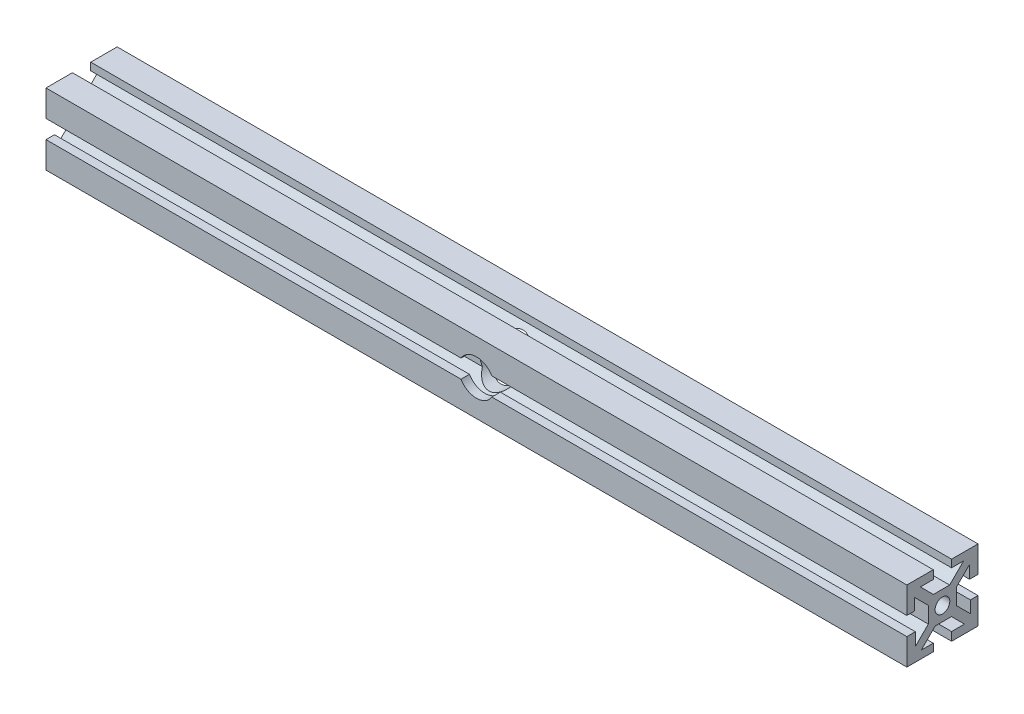
SolidWorks part; units mm, degrees
material "6061 Alloy"
ref_plane "Front Plane" through (0, 0, 0) normal (0, 0, 1) x (1, 0, 0)
ref_plane "Top Plane" through (0, 0, 0) normal (0, 1, 0) x (1, 0, 0)
ref_plane "Right Plane" through (0, 0, 0) normal (1, 0, 0) x (0, 0, -1)
sketch "Sketch1" plane through (0, 0, 0) normal (1, 0, 0) x (0, 0, -1)
  line L0 (2.5534, 5) -> (7.4749, 9.9215)
  line L1 (-5, 5) -> (5, 5)
  line L2 (-5, 5) -> (-5, -5)
  line L3 (-5, -5) -> (5, -5)
  line L4 (5, 5) -> (5, -5)
  line L5 (-5, 5) -> (5, -5) construction
  line L6 (-5, -5) -> (5, 5) construction
  line L7 (7.4749, 9.9215) -> (9.5962, 7.8001)
  line L8 (9.5962, 7.8001) -> (5, 3.2039)
  line L9 (5, 5) -> (13.6489, 13.6489) construction
  line L10 (7.4749, 9.9215) -> (3.24, 9.9215)
  line L11 (3.24, 9.9215) -> (3.24, 12.5962)
  line L12 (3.24, 12.5962) -> (12.5962, 12.5962)
  line L13 (9.5962, 7.8001) -> (9.5962, 3.24)
  line L14 (9.5962, 3.24) -> (12.5962, 3.24)
  line L15 (12.5962, 3.24) -> (12.5962, 12.5962)
  line L17 (0, 0) -> (0, 24.089) construction
  line L18 (0, 0) -> (23.75, 0) construction
  circle A0 centre (0, 0) radius 2.605
  point P0 (0, 0)
  dimension "D1" = 5.21
  dimension "D2" = 10
  dimension "D3" = 10
  dimension "D4" = 3
  dimension "D5" = 1.27
  dimension "D6" = 6.5
  dimension "D7" = 3.24
  dimension "D8" = 3.24
  dimension "D9" = 3
extrude "Boss-Extrude1" add sketch "Sketch1" along normal blind 304.8 contours L4 L1 L2 L3 A0 | L8 L7 L0 L1 L4 | L14 L15 L12 L11 L10 L7 L13 region at (0, 4.8586, -3.7767) region at (0, 6.7479, -6.3823) region at (0, 9.18, -9.3105)
ref_axis "Axis1" through (0, 0, 0) along (1, 0, 0)
pattern_circular "CirPattern1" count 4 over 360 about axis through (0, 0, 0) along (1, 0, 0) of "Boss-Extrude1"
sketch "Sketch2" plane through (0, 0, 0) normal (0, 0, 1) x (1, 0, 0)
  circle A0 centre (152.4, 0) radius 6.35
  dimension "D2" = 12.7
  dimension "D1" = 152.4
extrude "Cut-Extrude1" cut sketch "Sketch2" along normal blind 20 and the other way blind 30
